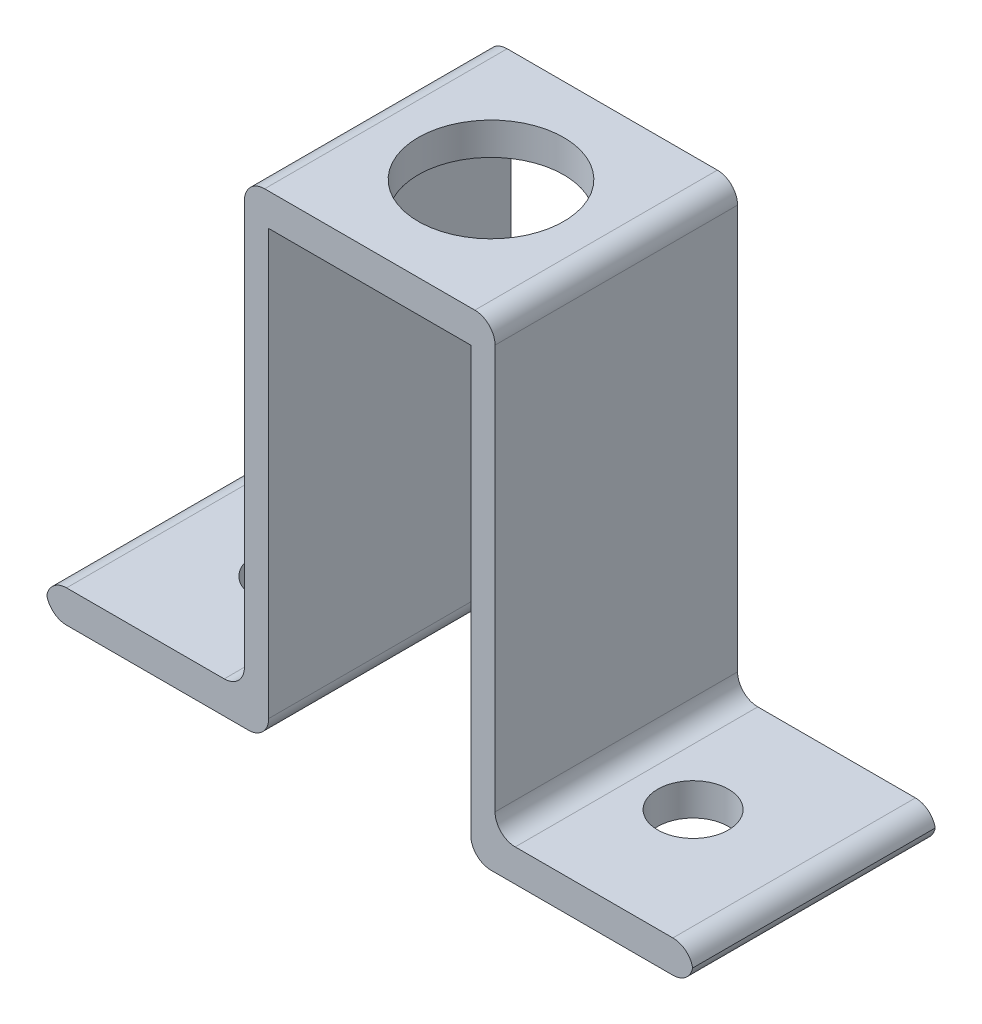
SolidWorks part; units mm, degrees
ref_plane "Front Plane" through (0, 0, 0) normal (0, 0, 1) x (1, 0, 0)
ref_plane "Top Plane" through (0, 0, 0) normal (0, 1, 0) x (1, 0, 0)
ref_plane "Right Plane" through (0, 0, 0) normal (1, 0, 0) x (0, 0, -1)
sketch "Sketch2" plane through (0, 0, 0) normal (0, 0, 1) x (1, 0, 0)
  line L1 (-5, 0) -> (5, 0)
  line L2 (-6.2, -20.4) -> (-6.2, 1.6)
  line L3 (-6.2, 1.6) -> (6.2, 1.6)
  line L4 (6.2, -20.4) -> (6.2, 1.6)
  line L15 (-6.2, -20.4) -> (-16, -20.4)
  line L16 (-5, 0) -> (-5, -22)
  line L17 (-5, -22) -> (-16, -22)
  line L18 (-16, -20.4) -> (-16, -22)
  line L19 (6.2, -20.4) -> (16, -20.4)
  line L20 (5, 0) -> (5, -22)
  line L21 (5, -22) -> (16, -22)
  line L22 (16, -20.4) -> (16, -22)
  point P0 (0, 0)
  point P23 (-5, -11)
  point P26 (0, 0)
  dimension "D1" = 32
  dimension "D2" = 10
  dimension "D3" = 1.6
  dimension "D4" = 1.2
  dimension "D5" = 1.6
  dimension "D6" = 22
extrude "Boss-Extrude1" add sketch "Sketch2" along normal blind 12
sketch "Sketch3" plane through (0, 1.6, 0) normal (0, 1, 0) x (1, 0, 0)
  line L0 (-6.2, -6) -> (6.2, -6) construction
  line L1 (-6.2, -12) -> (-6.2, 0) construction
  line L2 (6.2, -12) -> (6.2, 0) construction
  line L4 (0, 0) -> (0, -12) construction
  line L5 (6.2, -12) -> (-6.2, -12) construction
  circle A0 centre (0, -6) radius 3.6
  dimension "D1" = 7.2
extrude "Cut-Extrude1" cut sketch "Sketch3" against normal through all
sketch "Sketch5" plane through (0, -20.4, 0) normal (0, 1, 0) x (1, 0, 0)
  line L0 (-10, -6) -> (10, -6) construction
  line L3 (0, 0) -> (0, -12) construction
  line L6 (6.2, 0) -> (-6.2, 0) construction
  line L7 (6.2, -12) -> (-6.2, -12) construction
  circle A0 centre (-10, -6) radius 1.75
  circle A1 centre (10, -6) radius 1.75
  point P2 (0, -6)
  dimension "D1" = 3.5
  dimension "D2" = 20
extrude "Cut-Extrude2" cut sketch "Sketch5" against normal through all
fillet "Fillet1" radius 1 10 edges at (16, -20.4, 6) (-16, -22, 6) (16, -22, 6) (-16, -20.4, 6) (-6.2, -20.4, 6) (-6.2, 1.6, 6) (6.2, 1.6, 6) (6.2, -20.4, 6) (5, -22, 6) (-5, -22, 6)
